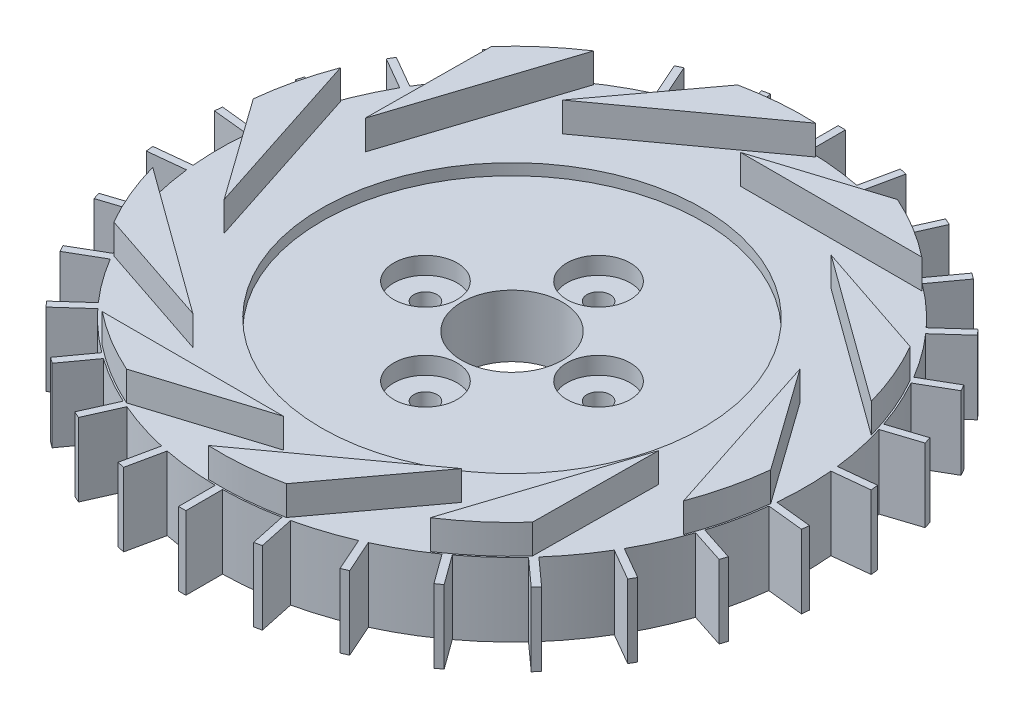
SolidWorks part; units mm, degrees
material "6061-T6 (SS)"
ref_plane "Front Plane" through (0, 0, 0) normal (0, 0, 1) x (1, 0, 0)
ref_plane "Top Plane" through (0, 0, 0) normal (0, 1, 0) x (1, 0, 0)
ref_plane "Right Plane" through (0, 0, 0) normal (1, 0, 0) x (0, 0, -1)
sketch "Sketch1" plane through (0, 0, 0) normal (1, 0, 0) x (0, 0, -1)
  line L0 (0, 26.2631) -> (0, -3.5886) construction
  line L1 (0, -3.5886) -> (-50.8, -3.5886)
  line L2 (-50.8, -3.5886) -> (-50.8, 9.1114)
  line L3 (-33.0001, 9.1114) -> (-50.8, 9.1114)
  line L4 (-33.0001, 9.1114) -> (-33.0001, 7.1515)
  line L5 (-33.0001, 7.1515) -> (0, 7.1515)
  line L6 (0, 7.1515) -> (0, -3.5886)
  dimension "D1" = 33.0001
  dimension "D2" = 50.8
  dimension "D3" = 1.96
  dimension "D4" = 12.7
revolve "Revolve1" add sketch "Sketch1" angle 360 about L0
sketch "Sketch2" plane through (0, 9.1114, 0) normal (0, 1, 0) x (1, 0, 0)
  line L8 (0, 39.6001) -> (19.9397, 39.6001) construction
  line L9 (0, 39.6001) -> (20.682, 46.1211)
  line L10 (0, 39.6001) -> (31.4123, 39.6001)
  arc A3 (20.682, 46.1211) -> (31.4123, 39.6001) centre (0, 0) cw
  circle A5 centre (0, 0) radius 33.0001 construction
  circle A7 centre (0, 0) radius 39.6001 construction
  point P9 (-2.4416, -40.4611)
  dimension "D1" = 66.0001
  dimension "D2" = 79.2001
  dimension "D4" = 50.546
  dimension "D3" = 17.5
extrude "Boss-Extrude1" add sketch "Sketch2" along normal blind 5.08
pattern_circular "CirPattern1" count 10 over 360 about axis through (0, 9.1114, 0) along (0, 1, 0) of "Boss-Extrude1"
ref_plane "Plane1" through (0, 0, 49.53) normal (0, 0, 1) x (1, 0, 0)
sketch "Sketch3" plane through (0, 0, 49.53) normal (0, 0, 1) x (1, 0, 0)
  line L0 (0, 0) -> (0, 9.7621) construction
  line L1 (0, -9.779) -> (0, 9.779) construction
  line L6 (-50.8, -3.5886) -> (50.8, -3.5886) construction
  line L13 (10.3772, 9.1114) -> (23.2763, 9.1114) construction
  line L14 (-0.635, -3.5886) -> (0.635, -3.5886)
  line L15 (-0.635, -3.5886) -> (-0.635, 9.1114)
  line L16 (-0.635, 9.1114) -> (0.635, 9.1114)
  line L17 (0.635, -3.5886) -> (0.635, 9.1114)
  point P11 (0, 9.1114)
  dimension "D1" = 1.27
extrude "Boss-Extrude2" add sketch "Sketch3" along normal blind 7.62 and the other way blind 0.254
pattern_circular "CirPattern16" count 30 over 360 about axis through (0, -3.5886, 0) along (0, 1, 0) of "Boss-Extrude2"
sketch "Sketch4" plane through (0, 7.1515, 0) normal (0, 1, 0) x (1, 0, 0)
  circle A0 centre (0, 0) radius 8.7312
  dimension "D1" = 17.4625
extrude "Cut-Extrude1" cut sketch "Sketch4" against normal up to next
sketch "Sketch5" plane through (0, -3.5886, 0) normal (0, -1, 0) x (-1, 0, 0)
  circle A0 centre (0, 0) radius 44.45
  dimension "D1" = 88.9
extrude "Cut-Extrude2" cut sketch "Sketch5" against normal blind 6.35
sketch "Sketch6" plane through (0, 2.7614, 0) normal (0, -1, 0) x (1, 0, 0)
  circle A0 centre (0, 0) radius 19.05
  circle A1 centre (0, 0) radius 8.7312 construction
  circle A2 centre (0, 0) radius 8.7312
  dimension "D1" = 38.1
extrude "Boss-Extrude3" add sketch "Sketch6" along normal up to surface (6.35 mm away) up to face at (0, -3.5886, -44.45)
sketch "Sketch9" plane through (0, 7.1515, 0) normal (0, 1, 0) x (1, 0, 0)
  circle A0 centre (0, 15) radius 2
  dimension "D1" = 4
  dimension "D2" = 15
extrude "Cut-Extrude3" cut sketch "Sketch9" against normal up to next
pattern_circular "CirPattern17" count 4 over 360 about axis through (0, 7.1515, 0) along (0, 1, 0) of "Cut-Extrude3"
ref_plane "Plane2" through (51.9838, 0, -23.1447) normal (-0.9135, 0, 0.4067) x (0.4067, 0, 0.9135)
sketch "Sketch10" plane through (51.9838, 0, -23.1447) normal (-0.9135, 0, 0.4067) x (0.4067, 0, 0.9135)
  line L0 (3.175, -3.5886) -> (3.175, -0.4136)
  line L1 (-46.1462, -3.5886) -> (-41.4681, -3.5886) construction
  line L2 (-3.175, -0.4136) -> (-3.175, -3.5886)
  line L3 (-3.175, -3.5886) -> (3.175, -3.5886)
  arc A0 (3.175, -0.4136) -> (-3.175, -0.4136) centre (0, -0.4136) ccw
  dimension "D1" = 3.175
  dimension "D2" = 3.175
sketch "Sketch11" plane through (0, 7.1515, 0) normal (0, 1, 0) x (1, 0, 0)
  circle A0 centre (0, -15) radius 5.5
  circle A1 centre (-15, 0) radius 5.5
  circle A2 centre (0, 15) radius 5.5
  circle A3 centre (15, 0) radius 5.5
  dimension "D1" = 11
extrude "Cut-Extrude5" cut sketch "Sketch11" against normal blind 3
ref_plane "Plane3" through (0, 16.7314, 0) normal (0, 1, 0) x (1, 0, 0)
ref_axis "Axis4" through (0, -3.5886, 0) along (0, 1, 0)
ref_point "Point1"
